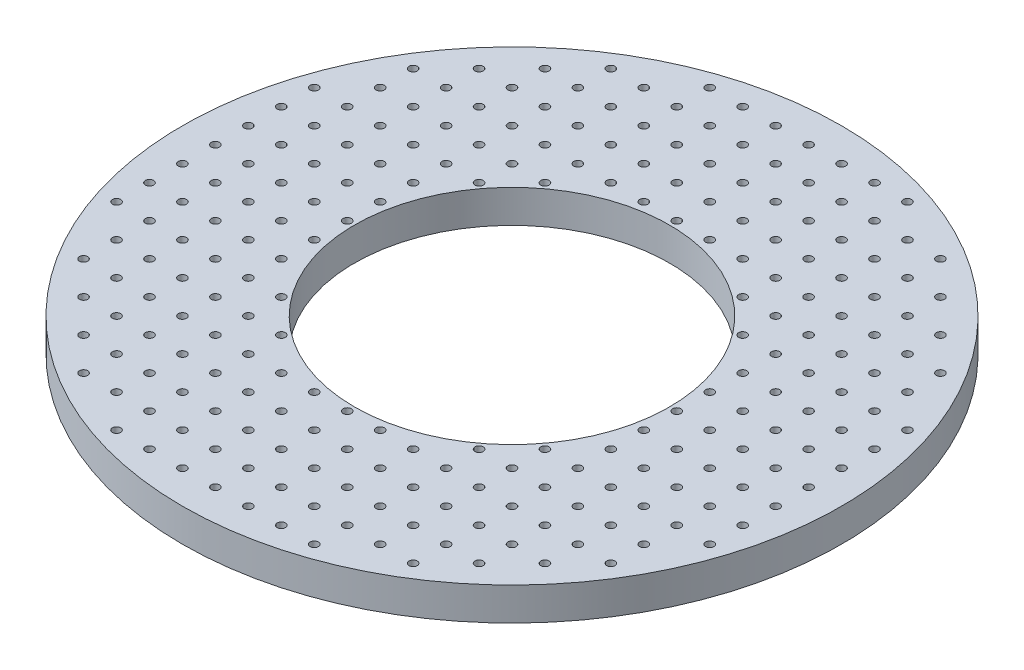
SolidWorks part; units mm, degrees
material "6061-T6 (SS)"
ref_plane "Front Plane" through (0, 0, 0) normal (0, 0, 1) x (1, 0, 0)
ref_plane "Top Plane" through (0, 0, 0) normal (0, 1, 0) x (1, 0, 0)
ref_plane "Right Plane" through (0, 0, 0) normal (1, 0, 0) x (0, 0, -1)
sketch "Sketch1" plane through (0, 0, 0) normal (0, 1, 0) x (1, 0, 0)
  circle A0 centre (0, 0) radius 254
  dimension "D1" = 508
extrude "Boss-Extrude1" add sketch "Sketch1" along normal blind 25.4
hole_wizard "1/4 (0.25) Diameter Hole2" positions "3DSketch3" profile "Sketch6" hole size "1/4" standard "ANSI Inch" end condition through all
sketch3d "3DSketch3"
  line L0 (0, 25.4, 0) -> (0, 0, 0) construction
  point P0 (0, 25.4, 0)
sketch "Sketch6" plane through (0, 25.4, 0) normal (1, 0, 0) x (0, 0, 1)
  line L0 (0, 0) -> (0, 25.4)
  line L1 (0, 25.4) -> (3.175, 25.4)
  line L2 (3.175, 25.4) -> (3.175, 0)
  line L5 (3.175, 0) -> (0, 0)
  line L11 (0, -6.35) -> (0, 107.95) construction
  dimension "Thru Hole Dia." = 6.35
  dimension "Thru Hole Depth" = 25.4
pattern_linear "LPattern1" count 10 spacing 25.4 along (0, 0, 1) count 10 spacing 25.4 along (1, 0, 0) skipping (4, 9), (6, 8), (7, 7), (8, 6), (9, 4) of "1/4 (0.25) Diameter Hole2"
mirror "Mirror1" about plane through (0, 0, 0) normal (1, 0, 0) of "LPattern1"
mirror "Mirror2" about plane through (0, 0, 0) normal (0, 0, 1) of "Mirror1", "LPattern1"
sketch "Sketch20" plane through (0, 25.4, 0) normal (0, 1, 0) x (1, 0, 0)
  circle A0 centre (0, 0) radius 121.4438
  dimension "D1" = 242.8875
extrude "Cut-Extrude2" cut sketch "Sketch20" against normal up to next
